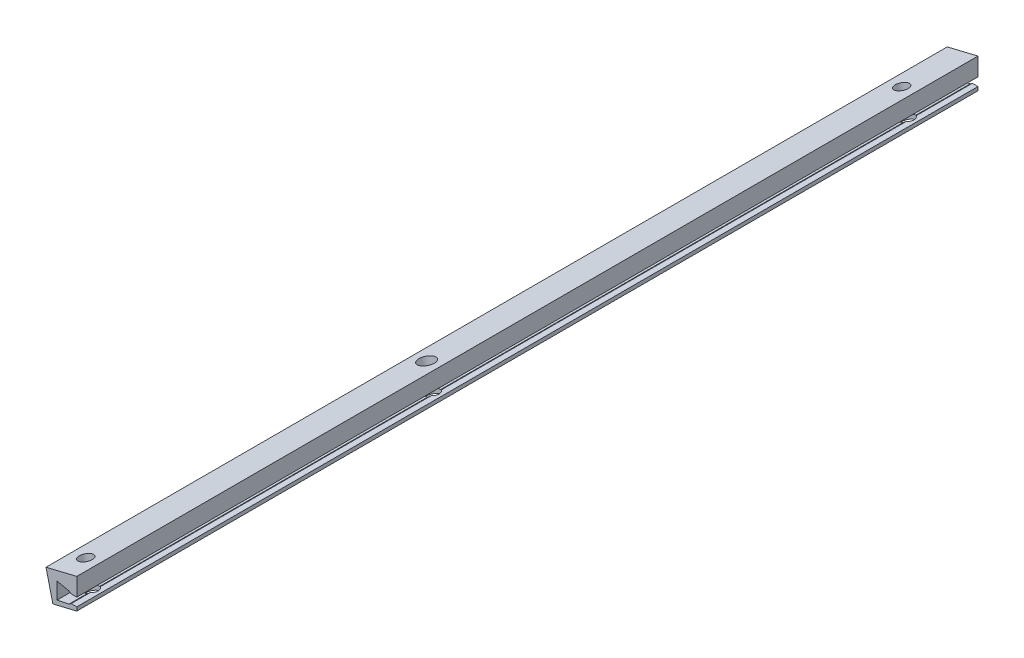
SolidWorks part; units mm, degrees
material "PET"
ref_plane "Front Plane" through (0, 0, 0) normal (0, 0, 1) x (1, 0, 0)
ref_plane "Top Plane" through (0, 0, 0) normal (0, 1, 0) x (1, 0, 0)
ref_plane "Right Plane" through (0, 0, 0) normal (1, 0, 0) x (0, 0, -1)
sketch "Sketch1" plane through (0, 0, 0) normal (0, 0, 1) x (1, 0, 0)
  line L0 (54.8024, -4.4013) -> (54.8024, 4.6665)
  line L2 (56.8344, 4.6665) -> (61.9906, 3.5705)
  line L3 (61.9906, 3.5705) -> (61.9906, 1.2248)
  line L4 (61.9906, 1.2248) -> (60.5247, 1.2248)
  line L6 (59.9586, 1.6211) -> (56.8344, 2.2852)
  line L7 (56.8344, 2.2852) -> (56.8344, -2.0201)
  line L8 (56.8344, -2.0201) -> (59.9586, -1.356)
  line L10 (60.5247, -0.9596) -> (61.9906, -0.9596)
  line L11 (61.9906, -0.9596) -> (61.9906, -3.3053)
  line L12 (61.9906, -3.3053) -> (56.8344, -4.4013)
  line L13 (56.8344, -4.4013) -> (54.8024, -4.4013)
  line L16 (54.8024, 4.6665) -> (56.8344, 4.6665)
  line L17 (59.9586, 1.6211) -> (60.5247, 1.2248)
  line L18 (56.8344, 0.1326) -> (54.8024, 0.1326) construction
  line L19 (59.9586, -1.356) -> (60.5247, -0.9596)
  point P10 (0, 0)
extrude "Boss-Extrude1" add sketch "Sketch1" along normal up to surface (237.2484 mm away)
sketch "Sketch2" plane through (0, 0, 0) normal (0, 0, -1) x (-1, 0, 0)
  line L5 (-54.8112, 4.1772) -> (-61.9906, 5.9135)
  line L6 (-61.9906, 5.9135) -> (-61.9906, 3.5705)
  line L7 (-61.9906, 3.5705) -> (-56.8344, 4.6665)
  line L8 (-54.8112, 4.1772) -> (-54.8024, 4.6665)
  line L9 (-54.8024, 4.6665) -> (-56.8344, 4.6665)
  line M3 (-54.8024, 4.6665) -> (-56.8344, 4.6665)
  line M4 (-56.8344, 4.6665) -> (-61.9906, 3.5705)
extrude "Boss-Extrude2" add sketch "Sketch2" against normal up to surface (237.2484 mm away) contours L5 L6 M4 region at (60.2719, 4.7168, 0) up to face at (58.9908, 0.1326, 237.2484)
extrude "Cut-Extrude1" cut sketch "Sketch2<3>" against normal through all contours L5 L8 M3 region at (55.4827, 4.5034, 0)
sketch "Sketch2<3>" plane through (0, 0, 0) normal (0, 0, -1) x (-1, 0, 0) same geometry as "Sketch2"
other "DeleteFace1" face at (54.8068, 4.4218, 118.6242) and patch yes
sketch "Sketch4" plane through (0, 0, 237.2484) normal (0, 0, 1) x (1, 0, 0)
  line L13 (61.9906, 5.9135) -> (54.8024, 4.175)
  line L14 (54.8024, 4.175) -> (54.8024, -4.4013)
  line L15 (54.8024, -4.4013) -> (56.8344, -4.4013)
  line L16 (56.8344, -4.4013) -> (61.9906, -3.3053)
  line L17 (61.9906, -3.3053) -> (61.9906, -0.9596)
  line L18 (61.9906, -0.9596) -> (60.5247, -0.9596)
  line L19 (60.5247, -0.9596) -> (59.9586, -1.356)
  line L20 (59.9586, -1.356) -> (56.8344, -2.0201)
  line L21 (56.8344, -2.0201) -> (56.8344, 2.2852)
  line L22 (56.8344, 2.2852) -> (59.9586, 1.6211)
  line L23 (59.9586, 1.6211) -> (60.5247, 1.2248)
  line L24 (60.5247, 1.2248) -> (61.9906, 1.2248)
  line L25 (61.9906, 1.2248) -> (61.9906, 5.9135)
  line L26 (61.9906, 5.9135) -> (54.8024, 4.175)
  line L27 (54.8024, 4.175) -> (54.8024, -4.4013)
  line L28 (54.8024, -4.4013) -> (56.8344, -4.4013)
  line L29 (56.8344, -4.4013) -> (61.9906, -3.3053)
  line L30 (61.9906, -3.3053) -> (61.9906, -0.9596)
  line L31 (61.9906, -0.9596) -> (60.5247, -0.9596)
  line L32 (60.5247, -0.9596) -> (59.9586, -1.356)
  line L33 (59.9586, -1.356) -> (56.8344, -2.0201)
  line L34 (56.8344, -2.0201) -> (56.8344, 2.2852)
  line L35 (56.8344, 2.2852) -> (59.9586, 1.6211)
  line L36 (59.9586, 1.6211) -> (60.5247, 1.2248)
  line L37 (60.5247, 1.2248) -> (61.9906, 1.2248)
  line L38 (61.9906, 1.2248) -> (61.9906, 5.9135)
  dimension "D1" = 0
extrude "Cut-Extrude2" cut sketch "Sketch4" against normal blind 2.3369
hole_wizard "#4 Clearance Hole1" positions "Sketch7" profile "Sketch8" hole size "#4" standard "ANSI Inch" end condition through all
sketch "Sketch7" plane through (2.0744, -8.5772, 0) normal (-0.2351, 0.972, 0) x (0.972, 0.2351, 0)
  point P0 (57.5161, -228.5615)
  point P2 (57.5161, -139.7)
  point P4 (57.5161, -15.875)
  point P7 (0, 0)
  point P10 (0, 0)
  point P13 (0, 0)
sketch "Sketch8" plane through (57.9788, 4.9432, 228.5615) normal (0, 0, 1) x (-0.972, -0.2351, 0)
  line L0 (0, 0) -> (0, 10.0258)
  line L1 (0, 10.0258) -> (1.7272, 10.0258)
  line L2 (1.7272, 10.0258) -> (1.7272, 0)
  line L5 (1.7272, 0) -> (0, 0)
  line L11 (0, -6.35) -> (0, 107.95) construction
  dimension "Thru Hole Dia." = 3.4544
  dimension "Thru Hole Depth" = 10.0258
hole_wizard "Hole1" positions "Sketch5" profile "Sketch6" legacy
sketch "Sketch5" plane through (2.0744, -8.5772, 0) normal (-0.2351, 0.972, 0) x (0.972, 0.2351, 0)
  point P3 (57.5161, -139.7)
sketch "Sketch6" plane through (57.9788, 4.9432, 139.7) normal (0, 0, 1) x (-0.972, -0.2351, 0)
  line L0 (0, 0) -> (0, 3.429)
  line L1 (0, 3.429) -> (1.9431, 3.429)
  line L2 (1.9431, 3.429) -> (2.0701, 0)
  line L3 (2.0701, 0) -> (0, 0)
  line L4 (0, 110) -> (0, -10) construction
  dimension "Minor Diameter" = 3.8862
  dimension "Depth" = 3.429
  dimension "Major Diameter" = 4.1402
sketch "Sketch9" plane through (0, 0, 234.9115) normal (0, 0, 1) x (1, 0, 0)
  line L0 (54.8024, 4.175) -> (53.9669, 3.973)
  line L1 (54.8024, 4.175) -> (54.8024, -4.4013) construction
  line L2 (61.9906, 5.9135) -> (54.8024, 4.175) construction
  line L3 (53.9669, 3.973) -> (54.8024, 0.5184)
  line L4 (54.8024, 0.5184) -> (54.8024, 4.175)
  line L5 (53.5938, 5.516) -> (53.9669, 3.973) construction
  point P6 (53.9669, 3.973)
  point P8 (53.9669, 3.973)
extrude "Boss-Extrude4" add sketch "Sketch9" against normal through all
sketch "Sketch10" plane through (0, 0, 234.9115) normal (0, 0, 1) x (1, 0, 0)
  line L0 (54.8024, 0.5184) -> (55.7582, -3.4335)
  line L1 (55.7582, -3.4335) -> (61.9906, -1.9262)
  line L2 (61.9906, -3.3053) -> (61.9906, -0.9596) construction
  line L3 (61.9906, -1.9262) -> (61.9906, -3.3053)
  line L4 (61.9906, -3.3053) -> (56.8344, -4.4013)
  line L5 (56.8344, -4.4013) -> (54.8024, -4.4013)
  line L6 (54.8024, -4.4013) -> (54.8024, 0.5184)
  line L7 (61.9906, 5.9135) -> (53.9669, 3.973) construction
  line L8 (53.9669, 3.973) -> (61.9906, 5.9135) construction
  dimension "D1" = 7.62
extrude "Cut-Extrude3" cut sketch "Sketch10" against normal through all
